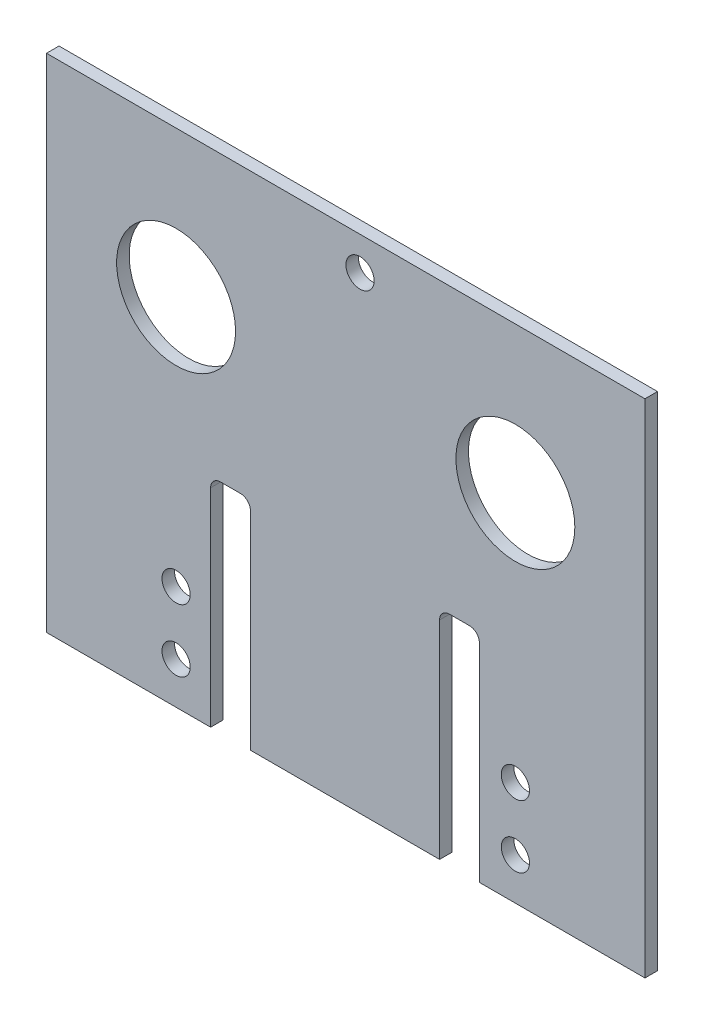
SolidWorks part; units mm, degrees
ref_plane "Front Plane" through (0, 0, 0) normal (0, 0, 1) x (1, 0, 0)
ref_plane "Top Plane" through (0, 0, 0) normal (0, 1, 0) x (1, 0, 0)
ref_plane "Right Plane" through (0, 0, 0) normal (1, 0, 0) x (0, 0, -1)
sketch "Sketch1" plane through (0, 0, 0) normal (0, 0, 1) x (1, 0, 0)
  line L1 (0, 0) -> (143.16, 0)
  line L2 (0, 0) -> (0, -120)
  line L3 (0, -120) -> (143.16, -120)
  line L4 (143.16, 0) -> (143.16, -120)
  dimension "D1" = 120
  dimension "D2" = 143.16
extrude "Boss-Extrude1" add sketch "Sketch1" along normal blind 3
sketch "Sketch2" plane through (0, 0, 3) normal (0, 0, 1) x (1, 0, 0)
  line L0 (0, 0) -> (0, -120) construction
  line L1 (143.16, -120) -> (143.16, 0) construction
  line L2 (0, -120) -> (143.16, -120) construction
  line L3 (143.16, 0) -> (0, 0) construction
  circle A0 centre (31, -35) radius 14.225
  circle A1 centre (112.16, -35) radius 14.225
  circle A3 centre (31, -110) radius 3.375
  circle A4 centre (112.16, -110) radius 3.375
  circle A7 centre (75, -8) radius 3.375
  circle A8 centre (31, -95) radius 3.375
  circle A9 centre (112.16, -95) radius 3.375
  dimension "D1" = 28.45
  dimension "D2" = 28.45
  dimension "D3" = 10
  dimension "D4" = 6.75
  dimension "D5" = 6.75
  dimension "D7" = 6.75
  dimension "D8" = 75
  dimension "D14" = 6.75
  dimension "D17" = 6.75
  dimension "D9" = 31
  dimension "D10" = 31
  dimension "D12" = 35
  dimension "D13" = 8
  dimension "D15" = 15
  dimension "D16" = 15
extrude "Cut-Extrude1" cut sketch "Sketch2" against normal through all
sketch "Sketch3" plane through (0, 0, 0) normal (0, 0, -1) x (-1, 0, 0)
  line L0 (-39.2577, -120) -> (-39.2577, -68)
  line L1 (0, -120) -> (-143.16, -120) construction
  line L2 (-39.2577, -68) -> (-48.7877, -68)
  line L3 (-48.7877, -68) -> (-48.7877, -120)
  line L4 (-48.7877, -120) -> (-39.2577, -120)
  line L5 (-103.5592, -120) -> (-103.5592, -68)
  line L6 (-103.5592, -68) -> (-94.0342, -68)
  line L7 (-94.0342, -68) -> (-94.0342, -120)
  line L8 (-94.0342, -120) -> (-103.5592, -120)
  point P8 (-39.2577, -69.2)
  point P11 (-103.5592, -69.2)
  dimension "D1" = 52
  dimension "D2" = 52
  dimension "D3" = 9.525
  dimension "D4" = 9.53
extrude "Cut-Extrude2" cut sketch "Sketch3" against normal through all
fillet "Fillet2" radius 2.3813 4 edges at (39.2577, -68, 1.5) (48.7877, -68, 1.5) (103.5592, -68, 1.5) (94.0342, -68, 1.5)
